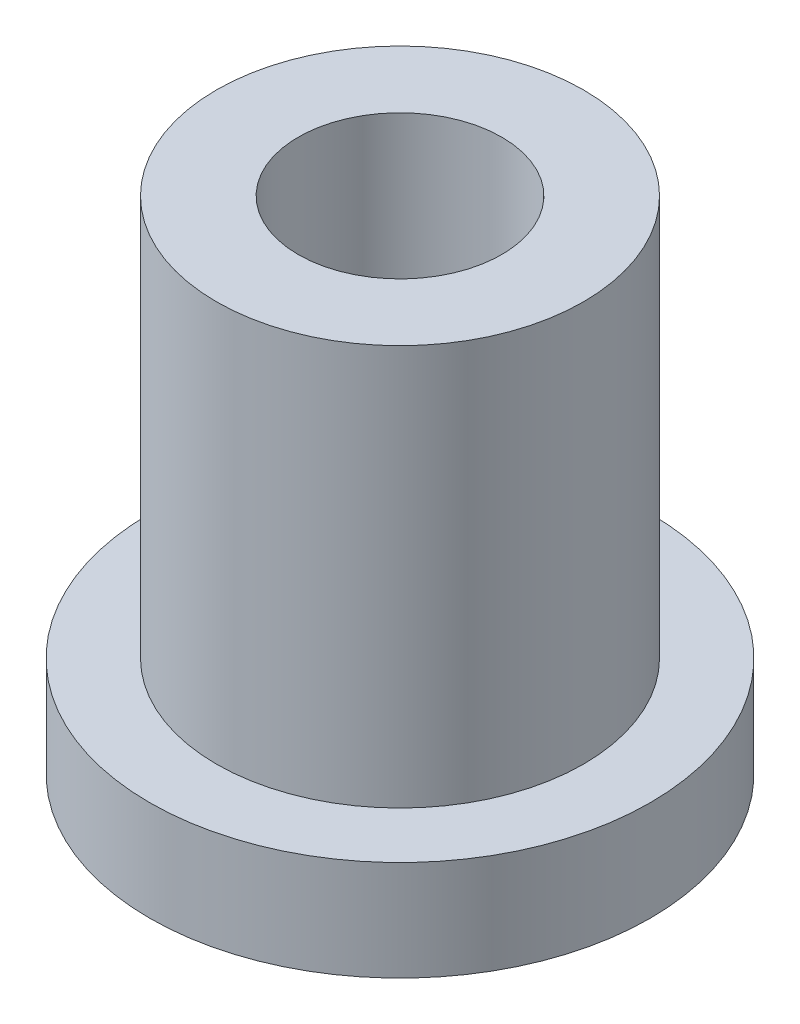
SolidWorks part; units mm, degrees
ref_plane "Front Plane" through (0, 0, 0) normal (0, 0, 1) x (1, 0, 0)
ref_plane "Top Plane" through (0, 0, 0) normal (0, 1, 0) x (1, 0, 0)
ref_plane "Right Plane" through (0, 0, 0) normal (1, 0, 0) x (0, 0, -1)
sketch "Sketch1" plane through (0, 0, 0) normal (0, 1, 0) x (1, 0, 0)
  circle A0 centre (0, 0) radius 7.5
  circle A1 centre (0, 0) radius 3.05
  dimension "D1" = 15
  dimension "D2" = 6.1
extrude "Boss-Extrude1" add sketch "Sketch1" along normal blind 3
ref_axis "Axis1" through (0, 0, -8.25) along (0, 0, 1)
sketch "Sketch3" plane through (0, 0, 0) normal (1, 0, 0) x (0, 0, -1)
  line L1 (4.35, 0) -> (5.75, 0)
  arc A0 (4.35, 0) -> (5.75, 0) centre (5.05, 0) ccw
  dimension "D1" = 2
  dimension "D2" = 1.4
revolve "Revolve2" add sketch "Sketch3" angle 360 about axis through (0, 0, -8.25) along (0, 0, 1)
ref_axis "Axis2" through (0, -0.885, 0) along (0, 1, 0)
pattern_circular "CirPattern1" count 10 over 360 about axis through (0, -0.885, 0) along (0, 1, 0) of "Revolve2"
sketch "Sketch4" plane through (0, 3, 0) normal (0, 1, 0) x (1, 0, 0)
  circle A0 centre (0, 0) radius 5.5
  circle A1 centre (0, 0) radius 3.05
  dimension "D1" = 11
extrude "Boss-Extrude2" add sketch "Sketch4" along normal blind 12
